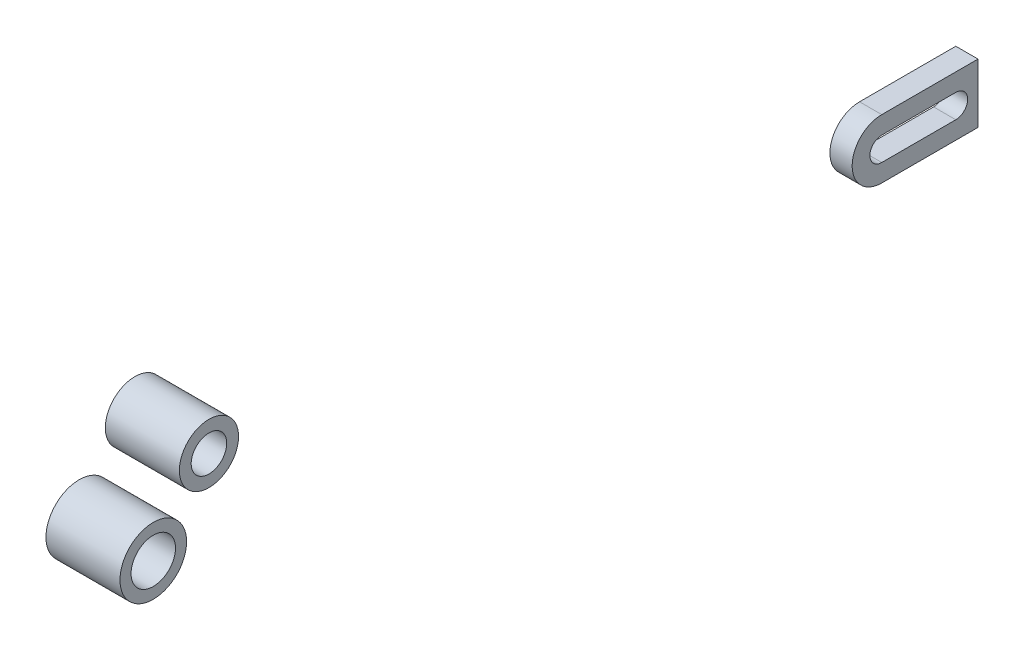
SolidWorks part; units mm, degrees
ref_plane "Płaszczyzna przednia" through (0, 0, 0) normal (0, 0, 1) x (1, 0, 0)
ref_plane "Płaszczyzna górna" through (0, 0, 0) normal (0, 1, 0) x (1, 0, 0)
ref_plane "Płaszczyzna prawa" through (0, 0, 0) normal (1, 0, 0) x (0, 0, -1)
sketch "Baza - płaszczyzna górna" plane through (0, 0, 0) normal (0, 1, 0) x (1, 0, 0)
  line L0 (0, 0) -> (0, 512) construction
  line L1 (117.5, 147.6) -> (-117.5, 147.6) construction
  line L2 (135, 0) -> (-135, 0) construction
  line L3 (-117.5, 512) -> (117.5, 512) construction
  line L4 (-117.5, 512) -> (-117.5, 147.6) construction
  line L5 (117.5, 512) -> (117.5, 147.6) construction
  line L6 (117.5, 186) -> (-117.5, 186) construction
  line L7 (135, 22.5) -> (135, -22.5) construction
  line L8 (-135, 22.5) -> (-135, -22.5) construction
  line L9 (117.5, 512) -> (125, 512) construction
  line L10 (125, 512) -> (125, 147.6) construction
  line L11 (125, 147.6) -> (117.5, 147.6) construction
  point P2 (0, 487)
  point P7 (0, 0)
  point P10 (0, 512)
  point P12 (0, 147.6)
  point P16 (135, 0)
  dimension "D1" = 512
  dimension "D2" = 147.6
  dimension "D3" = 270
  dimension "D4" = 235
  dimension "D5" = 326
  dimension "D6" = 45
  dimension "D7" = 25
  dimension "D8" = 125
sketch "Baza - płaszczyzna prawa" plane through (0, 0, 0) normal (1, 0, 0) x (0, 0, -1)
  line L0 (0, 0) -> (512, 0) construction
  line L1 (0, 0) -> (512, 0) construction
  line L2 (147.6, 0) -> (147.6, -66) construction
  arc A2 (440.6668, 297.4126) -> (440.6668, -297.4126) centre (487, 0) ccw
  dimension "D5" = 301
  dimension "D1" = 66
  dimension "D2" = 147.6
ref_plane "Powierzchnia styku z ramą" through (135, 0, 0) normal (1, 0, 0) x (0, 0, -1)
sketch "Szkic - insert - rama" plane through (135, 0, 0) normal (1, 0, 0) x (0, 0, -1)
  circle A0 centre (0, 0) radius 22.5
  circle A1 centre (0, 0) radius 15
  dimension "D1" = 45
  dimension "D2" = 30
ref_plane "Powierzchnia graniczna koła" through (125, 0, 0) normal (1, 0, 0) x (0, 0, -1)
ref_plane "Płaszczyzna pracy łańcucha" through (100, 0, 0) normal (1, 0, 0) x (0, 0, -1)
sketch "Łańcuch - baza" plane through (100, 0, 0) normal (1, 0, 0) x (0, 0, -1)
  line L0 (0, 0) -> (-72.4444, -19.4114) construction
  line L1 (0, 0) -> (512, 0) construction
  dimension "D1" = 75
  dimension "D2" = 165
sketch "Łańcuch - zarys" plane through (100, 0, 0) normal (1, 0, 0) x (0, 0, -1)
  line L0 (-75.0521, 2.4335) -> (503.4658, 71.4924)
  line L1 (-83.5151, 37.5222) -> (483.2736, 147.733)
  line L2 (-72.4444, -19.4114) -> (512, 0) construction
  line L3 (-79.7129, -76.9542) -> (493.1396, -149.3135)
  line L4 (-73.5969, -41.3812) -> (508.2284, -71.9011)
  circle A0 centre (-72.4444, -19.4114) radius 22
  circle A1 centre (512, 0) radius 72
  arc A2 (-83.5151, 37.5222) -> (-79.7129, -76.9542) centre (-72.4444, -19.4114) ccw
  arc A3 (493.1396, -149.3135) -> (483.2736, 147.733) centre (512, 0) ccw
  point P0 (-72.4444, -19.4114)
  point P2 (512, 0)
  dimension "D1" = 44
  dimension "D2" = 144
  dimension "D3" = 116
  dimension "D4" = 301
ref_axis "Oś tynego koła" through (-117.5, 0, -512) along (1, 0, 0)
ref_axis "Oś mocowania do ramy" through (135, 0, 0) along (-1, 0, 0)
ref_axis "Oś mocowania linkage" through (0, -66, -147.6) along (1, 0, 0)
sketch "Szkic - insert - linkage" plane through (0, 0, 0) normal (1, 0, 0) x (0, 0, -1)
  circle A0 centre (147.6, -66) radius 12
  circle A1 centre (147.6, -66) radius 20
  dimension "D1" = 40
  dimension "D2" = 24
extrude "Rama" add sketch "Szkic - insert - rama" against normal blind 50
extrude "Linkage" add sketch "Szkic - insert - linkage" along normal mid plane 50 separate body
sketch "Szkic - insert - tylne koło" plane through (125, 0, 0) normal (1, 0, 0) x (0, 0, -1)
  line L0 (487, 20) -> (552, 20)
  line L1 (512, 0) -> (147.6, 0) construction
  line L2 (487, -20) -> (552, -20)
  line L3 (537, 8) -> (487, 8)
  line L4 (537, -8) -> (487, -8)
  line L5 (552, -20) -> (552, 20)
  arc A1 (487, 8) -> (487, -8) centre (487, 0) ccw
  arc A2 (537, -8) -> (537, 8) centre (537, 0) ccw
  arc A3 (487, 20) -> (487, -20) centre (487, 0) ccw
  dimension "D1" = 40
  dimension "D3" = 8
  dimension "D2" = 65
  dimension "D4" = 487
  dimension "D5" = 537
extrude "Tylne koło" add sketch "Szkic - insert - tylne koło" along normal blind 15 separate body
